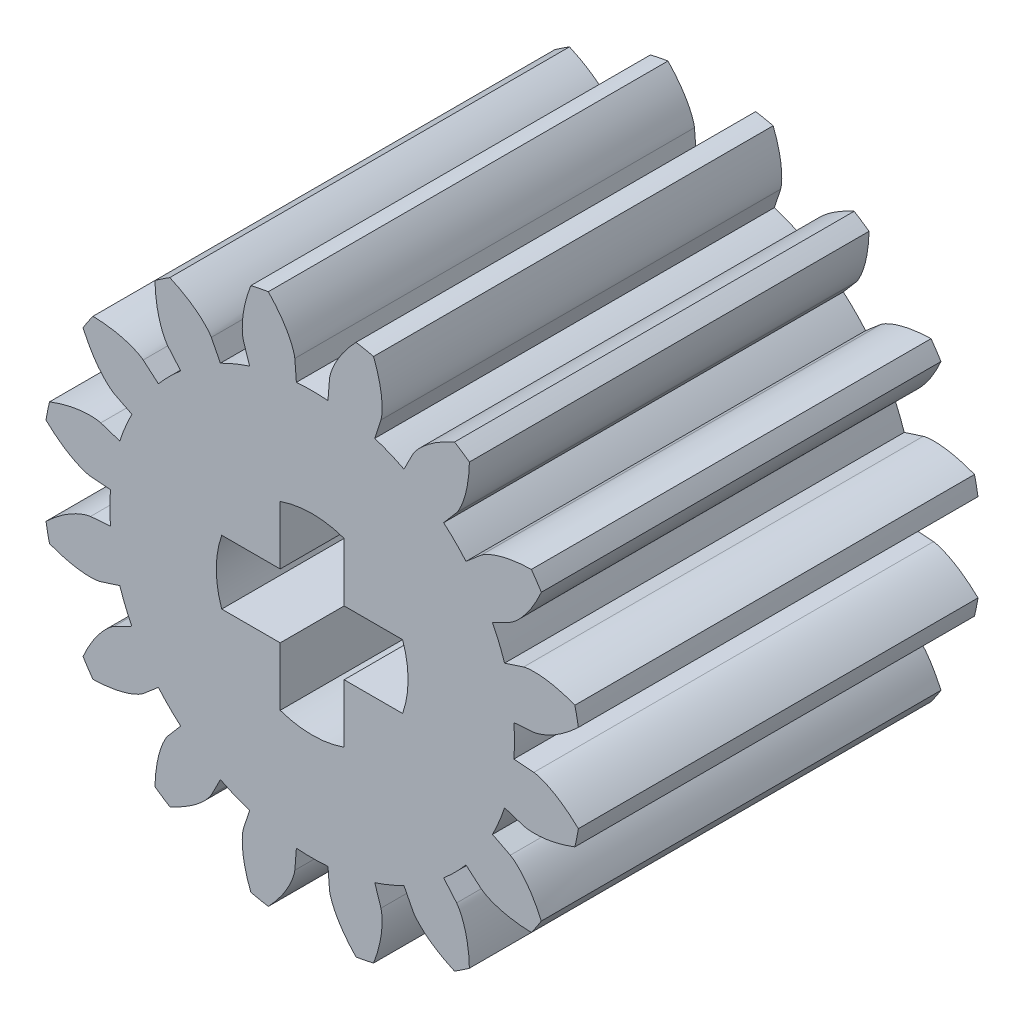
SolidWorks part; units mm, degrees
ref_plane "Front Plane" through (0, 0, 0) normal (0, 0, 1) x (1, 0, 0)
ref_plane "Top Plane" through (0, 0, 0) normal (0, 1, 0) x (1, 0, 0)
ref_plane "Right Plane" through (0, 0, 0) normal (1, 0, 0) x (0, 0, -1)
ref_axis "Axis1" [suppressed] through (0, 0, 71.2135) along (0, 0, -1)
sketch "Sketch1" plane through (0, 0, 0) normal (0, 0, 1) x (1, 0, 0)
  circle A0 centre (0, 0) radius 5.0625
  circle A1 centre (0, 0) radius 5.5631
  circle A2 centre (0, 0) radius 5.25
  circle A3 centre (0, 0) radius 6
  circle A4 centre (0, 0) radius 6.75
  dimension "Pitch" = 12
  dimension "Addendum" = 13.5
  dimension "Clearance" = 10.5
  dimension "Base" = 11.1262
  dimension "Root" = 10.125
extrude "Boss-Extrude1" add sketch "Sketch1" along normal blind 10 contours A4
sketch "Sketch3" plane through (0, 0, 0) normal (0, 0, 1) x (1, 0, 0)
  line L0 (0.4342, 5.5461) -> (0, 0) construction
  line L1 (0.868, 5.495) -> (0, 0) construction
  line L2 (1.2964, 5.4099) -> (0, 0) construction
  line L3 (1.7169, 5.2915) -> (0, 0) construction
  line L4 (2.1268, 5.1405) -> (0, 0) construction
  line L5 (2.5235, 4.9578) -> (0, 0) construction
  line L6 (2.9047, 4.7445) -> (0, 0) construction
  line L7 (3.268, 4.502) -> (0, 0) construction
  line L8 (3.6112, 4.2317) -> (0, 0) construction
  line L9 (3.9321, 3.9353) -> (0, 0) construction
  line L10 (4.2287, 3.6147) -> (0, 0) construction
  line L11 (0.868, 5.495) -> (0.4364, 5.5631) construction
  line L12 (4.2287, 3.6147) -> (1.3897, 6.9359) construction
  line L13 (1.2964, 5.4099) -> (0.4466, 5.6136) construction
  line L14 (1.7169, 5.2915) -> (0.4701, 5.6961) construction
  line L15 (2.1268, 5.1405) -> (0.5118, 5.8087) construction
  line L16 (2.5235, 4.9578) -> (0.5766, 5.9488) construction
  line L17 (2.9047, 4.7445) -> (0.6689, 6.1134) construction
  line L18 (3.268, 4.502) -> (0.7929, 6.2987) construction
  line L19 (3.6112, 4.2317) -> (0.9523, 6.5007) construction
  line L20 (3.9321, 3.9353) -> (1.1503, 6.7148) construction
  line L21 (0, 0) -> (0, 6) construction
  line L22 (0, 0) -> (0.5881, 5.9711)
  line L23 (0, 0) -> (-0.5881, 5.9711)
  line L24 (0.4342, 5.5461) -> (0.3951, 5.0471)
  line L25 (-0.4342, 5.5461) -> (-0.3951, 5.0471)
  circle A0 centre (0, 0) radius 5.5631 construction
  circle A1 centre (0, 0) radius 6 construction
  arc A2 (4.2287, 3.6147) -> (0.4342, 5.5461) centre (0, 0) ccw construction
  circle A3 centre (0, 0) radius 5.0625 construction
  circle A4 centre (0, 0) radius 5.0625
  circle A5 centre (0, 0) radius 6.75 construction
  circle A6 centre (0, 0) radius 6.75
  spline S0 degree 3 poles (0.4342, 5.5461) (0.4366, 5.5689) (0.447, 5.6194) (0.4724, 5.7074) (0.5146, 5.8199) (0.6112, 6.0273) (0.7582, 6.2606) (1.0245, 6.5969) (1.2334, 6.8022) (1.3897, 6.9359) knots 0 0 0 0 0.040008 0.090018 0.16003 0.250047 0.489907 0.639935 1 1 1 1
  spline S1 degree 3 poles (-0.4342, 5.5461) (-0.4366, 5.5689) (-0.447, 5.6194) (-0.4724, 5.7074) (-0.5146, 5.8199) (-0.6112, 6.0273) (-0.7582, 6.2606) (-1.0245, 6.5969) (-1.2334, 6.8022) (-1.3897, 6.9359) knots 0 0 0 0 0.040008 0.090018 0.16003 0.250047 0.489907 0.639935 1 1 1 1
  point P2 (0, 0)
  point P18 (0, 0)
  point P57 (3.4733, 44.1443)
  dimension "D2" = 45
  dimension "D3" = 0.4369
  dimension "D4" = 4.3693
  dimension "D5" = 0.8739
  dimension "D6" = 1.3108
  dimension "D7" = 1.7477
  dimension "D8" = 2.1846
  dimension "D9" = 2.6216
  dimension "D10" = 3.0585
  dimension "D11" = 3.4954
  dimension "D12" = 3.9323
  dimension "D13" = 11.25
  dimension "D1" = 11
extrude "Cut-Extrude3" cut sketch "Sketch3" along normal through all contours S1 L25 A4 L24 S0 A6 region at (0, 6.0519, 0)
pattern_circular "CirPattern1" count 16 over 360 about axis through (0, 0, 71.2135) along (0, 0, -1) of "Cut-Extrude3"
sketch "Sketch5" plane through (0, 0, 0) normal (0, 0, 1) x (1, 0, 0)
  line L0 (-2.2627, 0.8) -> (-0.8, 0.8) construction
  line L1 (-0.8, -0.8) -> (-2.2627, -0.8) construction
  line L2 (-0.8, -2.2627) -> (-0.8, -0.8) construction
  line L3 (0.8, -0.8) -> (0.8, -2.2627) construction
  line L4 (2.2627, -0.8) -> (0.8, -0.8) construction
  line L5 (0.8, 0.8) -> (2.2627, 0.8) construction
  line L6 (0.8, 2.2627) -> (0.8, 0.8) construction
  line L7 (-0.8, 0.8) -> (-0.8, 2.2627) construction
  line L8 (-2.2627, 0.8) -> (-0.8, 0.8)
  line L9 (-0.8, -0.8) -> (-2.2627, -0.8)
  line L10 (-0.8, -2.2627) -> (-0.8, -0.8)
  line L11 (0.8, -0.8) -> (0.8, -2.2627)
  line L12 (2.2627, -0.8) -> (0.8, -0.8)
  line L13 (0.8, 0.8) -> (2.2627, 0.8)
  line L14 (0.8, 2.2627) -> (0.8, 0.8)
  line L15 (-0.8, 0.8) -> (-0.8, 2.2627)
  arc A0 (-2.2627, 0.8) -> (-2.2627, -0.8) centre (0, 0) ccw construction
  arc A1 (-0.8, -2.2627) -> (0.8, -2.2627) centre (0, 0) ccw construction
  arc A2 (2.2627, -0.8) -> (2.2627, 0.8) centre (0, 0) ccw construction
  arc A3 (0.8, 2.2627) -> (-0.8, 2.2627) centre (0, 0) ccw construction
  arc A4 (-2.2627, 0.8) -> (-2.2627, -0.8) centre (0, 0) ccw
  arc A5 (-0.8, -2.2627) -> (0.8, -2.2627) centre (0, 0) ccw
  arc A6 (2.2627, -0.8) -> (2.2627, 0.8) centre (0, 0) ccw
  arc A7 (0.8, 2.2627) -> (-0.8, 2.2627) centre (0, 0) ccw
extrude "Cut-Extrude4" cut sketch "Sketch5" along normal through all
equation "\"Module\" = .75"
equation "\"numTeeth\" = 16"
equation "\"pressureAngle\"= 22deg"
equation "\"toothRadius\"= 0.2"
equation "\"Pitch@Sketch1\"=\"Module\"*\"numTeeth\""
equation "\"Addendum@Sketch1\"=\"Pitch@Sketch1\"+\"Module\"*2"
equation "\"Clearance@Sketch1\"=\"Pitch@Sketch1\"-\"Module\"*2"
equation "\"Base@Sketch1\"=\"Pitch@Sketch1\"*cos(\"pressureAngle\")"
equation "\"Root@Sketch1\"=\"Pitch@Sketch1\"-\"Module\"*1.25*2"
equation "\"D4@Sketch3\"= \"Base@Sketch1\" * pi / 8"
equation "\"D3@Sketch3\"= \"D4@Sketch3\" / 10"
equation "\"D5@Sketch3\"=\"D3@Sketch3\"*2"
equation "\"D6@Sketch3\"=\"D3@Sketch3\"*3"
equation "\"D7@Sketch3\"=\"D3@Sketch3\"*4"
equation "\"D8@Sketch3\"=\"D3@Sketch3\"*5"
equation "\"D9@Sketch3\"=\"D3@Sketch3\"*6"
equation "\"D10@Sketch3\"=\"D3@Sketch3\"*7"
equation "\"D11@Sketch3\"=\"D3@Sketch3\"*8"
equation "\"D12@Sketch3\"=\"D3@Sketch3\"*9"
equation "\"D13@Sketch3\"=180/\"numTeeth\""
equation "\"D1@CirPattern1\"=\"numTeeth\""
